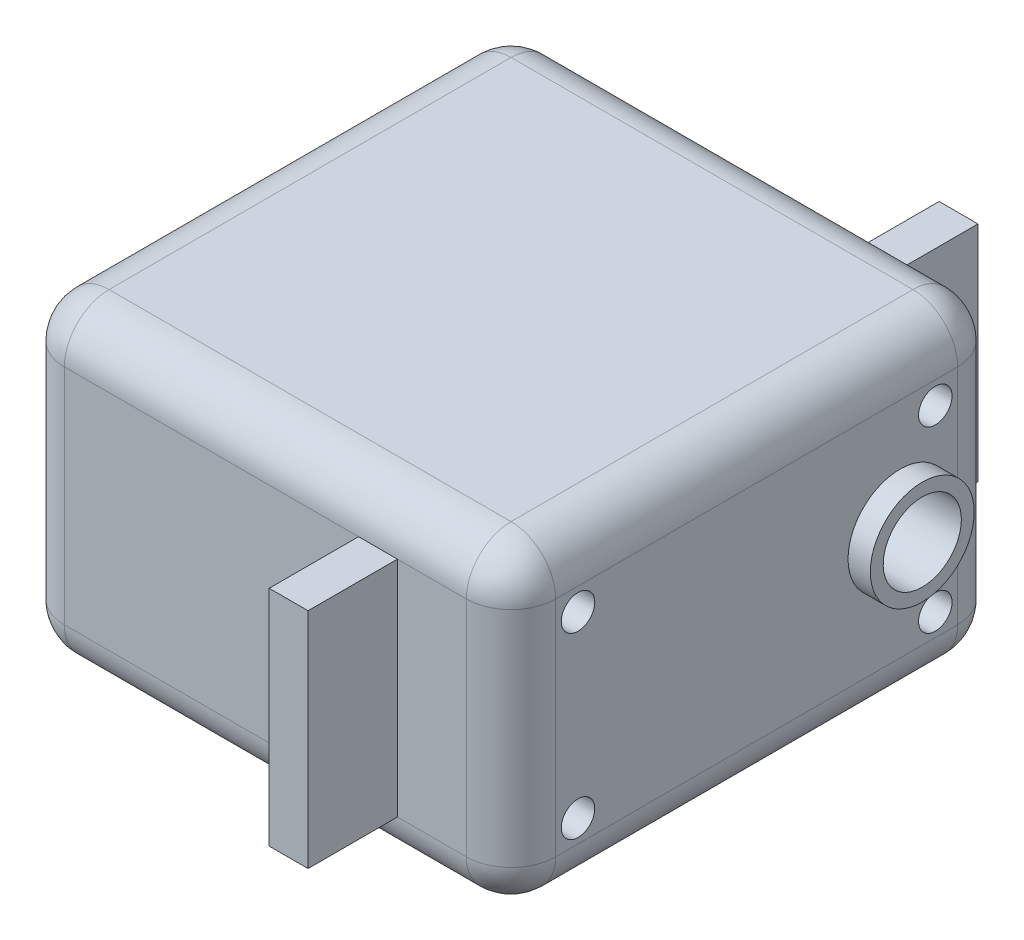
SolidWorks part; units mm, degrees
note: The reader was unsure of these and kept them because the rebuilt part matched: shared geometry of "Sketch5<2>".
ref_plane "Front Plane" through (0, 0, 0) normal (0, 0, 1) x (1, 0, 0)
ref_plane "Top Plane" through (0, 0, 0) normal (0, 1, 0) x (1, 0, 0)
ref_plane "Right Plane" through (0, 0, 0) normal (1, 0, 0) x (0, 0, -1)
sketch "Sketch1" plane through (0, 0, 0) normal (0, 0, 1) x (1, 0, 0)
  line L1 (-11, 7) -> (11, 7)
  line L2 (-11, 7) -> (-11, -7)
  line L3 (-11, -7) -> (11, -7)
  line L4 (11, 7) -> (11, -7)
  line L5 (-11, 7) -> (11, -7) construction
  line L6 (-11, -7) -> (11, 7) construction
  point P0 (0, 0)
  dimension "D1" = 14
  dimension "D2" = 22
extrude "Boss-Extrude1" add sketch "Sketch1" along normal mid plane 22
fillet "Fillet1" radius 2 12 edges at (0, -7, 11) (11, -7, 0) (11, 0, 11) (11, 7, 0) (0, 7, 11) (-11, 7, 0) (-11, 0, 11) (-11, -7, 0) (0, 7, -11) (-11, 0, -11) (0, -7, -11) (11, 0, -11)
sketch "Sketch4" plane through (11, 0, 0) normal (1, 0, 0) x (0, 0, -1)
  line L0 (9, -5) -> (9, 5) construction
  line L1 (-9, 5) -> (-9, -5) construction
  line L3 (-9, -5) -> (9, -5) construction
  line L4 (9, 5) -> (-9, 5) construction
  circle A0 centre (-8, 4) radius 0.75
  circle A1 centre (-8, -4) radius 0.75
  circle A2 centre (8, -4) radius 0.75
  circle A3 centre (8, 4) radius 0.75
  dimension "D1" = 1.5
  dimension "D2" = 1.5
  dimension "D3" = 1.5
  dimension "D4" = 1.5
  dimension "D5" = 1
  dimension "D6" = 1
  dimension "D7" = 1
  dimension "D8" = 1
extrude "Cut-Extrude1" cut sketch "Sketch4" against normal blind 28
sketch "Sketch5" plane through (11, 0, 0) normal (1, 0, 0) x (0, 0, -1)
  circle A0 centre (6.4164, 0) radius 2.3249
  circle A1 centre (6.4164, 0) radius 1.75
  dimension "D1" = 3.5
extrude "Boss-Extrude2" add sketch "Sketch5" along normal blind 1
extrude "Cut-Extrude2" cut sketch "Sketch5<2>" against normal blind 10 contours A1
sketch "Sketch5<2>" plane through (11, 0, 0) normal (1, 0, 0) x (0, 0, -1) same geometry as "Sketch5"
sketch "Sketch6" plane through (0, 0, -11) normal (0, 0, -1) x (-1, 0, 0)
  line L0 (9, 5) -> (-9, 5) construction
  line L1 (-5.9118, 5) -> (-4.1707, 5)
  line L2 (-5.9118, 5) -> (-5.9118, -5)
  line L3 (-5.9118, -5) -> (-4.1707, -5)
  line L4 (-4.1707, 5) -> (-4.1707, -5)
  line L5 (-9, -5) -> (9, -5) construction
extrude "Boss-Extrude3" add sketch "Sketch6" along normal blind 4 and the other way offset from surface (26 mm away) 4 other way up to face at (0, 0, 11)
